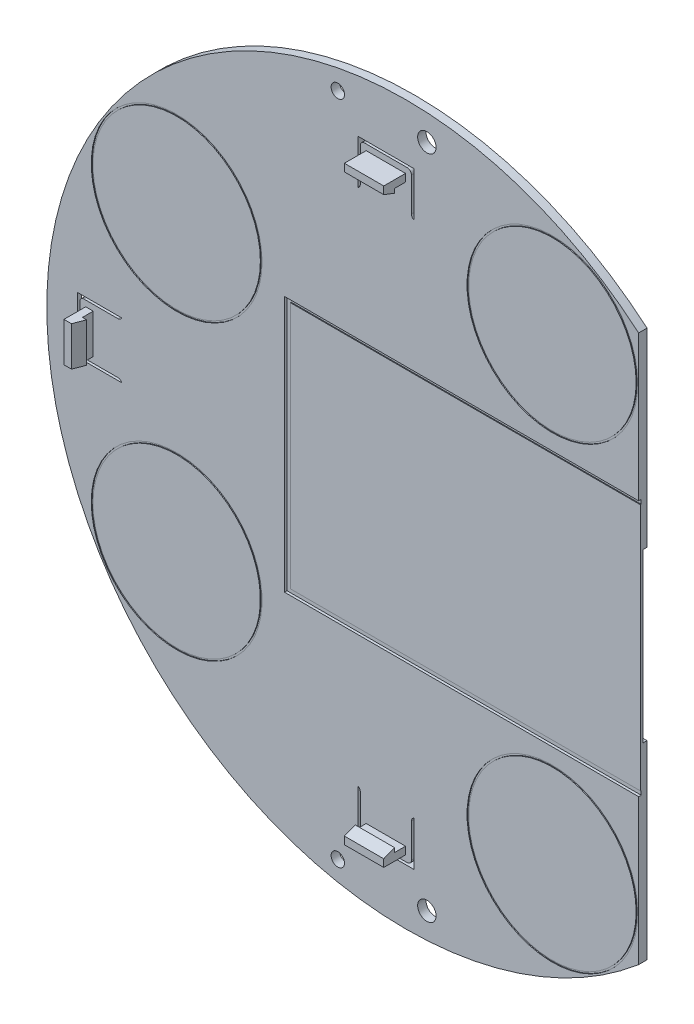
SolidWorks part; units mm, degrees
ref_plane "Front Plane" through (0, 0, 0) normal (1, 0, 0) x (0, 1, 0)
ref_plane "Top Plane" through (0, 0, 0) normal (0, 0, 1) x (0, 1, 0)
ref_plane "Right Plane" through (0, 0, 0) normal (0, 1, 0) x (-1, 0, 0)
sketch "Sketch1" plane through (0, 0, 0) normal (0, 0, 1) x (0, 1, 0)
  line L1 (0, 1.8938) -> (0, 57.7445) construction
  line L10 (65.3474, -55.6) -> (-65.3474, -55.6)
  circle A0 centre (-79.5, -5) radius 2.2
  arc A7 (65.3474, -55.6) -> (-65.3474, -55.6) centre (0, 0) ccw
  circle A9 centre (-79.5, 16.2726) radius 1.6
  circle A10 centre (79.5, 16.2726) radius 1.6
  circle A11 centre (79.5, -5) radius 2.2
  dimension "D1" = 85.8
  dimension "D2" = 55.6
  dimension "D3" = 5
  dimension "D4" = 79.5
  dimension "D5" = 16.2726
  dimension "D6" = 79.5
extrude "Boss-Extrude1" add sketch "Sketch1" along normal blind 2
sketch "Sketch3" plane through (0, 0, 2) normal (0, 0, 1) x (1, 0, 0)
  circle A0 centre (-54.772, 35.0004) radius 20
  circle A1 centre (-54.772, -35.0004) radius 20
  circle A2 centre (35, 54.7723) radius 20
  circle A3 centre (35, -54.7723) radius 20
  circle A5 centre (-54.772, 35.0004) radius 20.4
  circle A6 centre (-54.772, -35.0004) radius 20.4
  circle A7 centre (35, -54.7723) radius 20
  circle A9 centre (35, -54.7723) radius 20.4
  circle A10 centre (35, 54.7723) radius 20.4
extrude "Cut-Extrude9" cut sketch "Sketch3" against normal blind 0.2 contours A9 A3 | A10 A2 | A6 | A1 | A5 | A0 region at (14.6577, -54.7723, 2) region at (14.6577, 54.7723, 2)
sketch "Sketch6" plane through (0, 0, 2) normal (0, 0, 1) x (1, 0, 0)
  line L0 (-9.5, -70.5) -> (-9.5, -68.7)
  line L6 (-9.5, -70.5) -> (-0.1, -70.5)
  line L14 (-0.1, -70.5) -> (-0.1, -68.7)
  line L19 (-9.5, -68.7) -> (-0.1, -68.7)
  line L25 (0, 0) -> (-112.0525, 0) construction
  line L27 (-9.5, 68.7) -> (-0.1, 68.7)
  line L28 (-0.1, 70.5) -> (-0.1, 68.7)
  line L29 (-9.5, 70.5) -> (-0.1, 70.5)
  line L30 (-9.5, 70.5) -> (-9.5, 68.7)
  point P0 (-4.8, -69.9)
  point P11 (-4.8, 69.9)
extrude "Boss-Extrude2" add sketch "Sketch6" along normal blind 5.2
sketch "Sketch7" plane through (0, 0, 2) normal (0, 0, 1) x (1, 0, 0)
  line L0 (0, 0) -> (-76, 0) construction
  line L1 (-76.5, -4.7) -> (-76.5, 4.7)
  line L2 (-76.5, -4.7) -> (-74.7, -4.7)
  line L3 (-74.7, -4.7) -> (-74.7, 4.7)
  line L4 (-76.5, 4.7) -> (-74.7, 4.7)
extrude "Boss-Extrude3" add sketch "Sketch7" along normal blind 5.2
sketch "Sketch8" plane through (-0.1, 0, 0) normal (1, 0, 0) x (0, 1, 0)
  line L0 (-68.7, 7.2) -> (-68.7, 4.6)
  line L1 (-68.7, 7.2) -> (-68.7, 2) construction
  line L2 (-68.7, 4.6) -> (-67.7, 4.6)
  line L3 (-67.7, 4.6) -> (-68.7, 7.2)
  line L4 (0, 0) -> (0, 20.1599) construction
  line L5 (67.7, 4.6) -> (68.7, 7.2)
  line L6 (68.7, 4.6) -> (67.7, 4.6)
  line L7 (68.7, 7.2) -> (68.7, 4.6)
  line L8 (85.8, 2) -> (-85.8, 2) construction
  dimension "D1" = 1
  dimension "D2" = 2.6
extrude "Boss-Extrude4" add sketch "Sketch8" against normal blind 9.4
sketch "Sketch10" plane through (0, 0, 2) normal (0, 0, 1) x (1, 0, 0)
  line L0 (55.6, -29.6) -> (-28, -29.6)
  line L1 (55.6, -65.3474) -> (55.6, 65.3474) construction
  line L2 (55.6, 0) -> (-104.6824, 0) construction
  line L3 (-28, -29.6) -> (-28, 29.6)
  line L4 (55.6, -30.6) -> (-29, -30.6)
  line L5 (-29, -30.6) -> (-29, 30.6)
  line L6 (55.6, -30.6) -> (55.6, -29.6)
  line L7 (55.6, 30.6) -> (55.6, 29.6)
  line L8 (55.6, 30.6) -> (-29, 30.6)
  line L9 (55.6, 29.6) -> (-28, 29.6)
  point P14 (-29, 0)
  point P15 (-28, 0)
  dimension "D1" = 29.6
  dimension "D2" = 1
  dimension "D3" = 1
  dimension "D4" = 28
extrude "Cut-Extrude10" cut sketch "Sketch10" against normal blind 0.6
sketch "Sketch11" plane through (0, 0, 2) normal (0, 0, 1) x (1, 0, 0)
  line L1 (-28, 29.6) -> (55.6, 29.6)
  line L2 (-28, 29.6) -> (-28, -29.6)
  line L3 (-28, -29.6) -> (55.6, -29.6)
  line L4 (55.6, 29.6) -> (55.6, -29.6)
extrude "Cut-Extrude11" cut sketch "Sketch11" against normal blind 0.4
sketch "Sketch13" plane through (0, -4.7, 0) normal (0, -1, 0) x (1, 0, 0)
  line L0 (-74.7, 7.2) -> (-74.7, 4.6)
  line L1 (-74.7, 7.2) -> (-74.7, 2) construction
  line L2 (-74.7, 4.6) -> (-73.7, 4.6)
  line L3 (-73.7, 4.6) -> (-74.7, 7.2)
  line L4 (55.6, 2) -> (-85.8, 2) construction
  dimension "D1" = 1
  dimension "D2" = 2.6
extrude "Boss-Extrude5" add sketch "Sketch13" against normal blind 9.4
sketch "Sketch14" plane through (0, 0, 2) normal (0, 0, 1) x (1, 0, 0)
  line L0 (0.2, 71.5) -> (-9.8, 68.5) construction
  line L1 (-9.8, -71.5) -> (-9.8, -68.5)
  line L2 (-9.8, -71.5) -> (0.2, -71.5)
  line L3 (0.2, -71.5) -> (0.2, -68.5)
  line L4 (-9.8, -68.5) -> (0.2, -68.5)
  line L5 (-9.8, -71.5) -> (0.2, -68.5) construction
  line L6 (0.2, -71.5) -> (-9.8, -68.5) construction
  line L7 (-9.8, 71.5) -> (0.2, 68.5) construction
  line L8 (-9.8, 68.5) -> (0.2, 68.5)
  line L9 (0, 0) -> (-76, 0) construction
  line L10 (-77.5, -5) -> (-77.5, 5)
  line L11 (-77.5, -5) -> (-74.5, -5)
  line L12 (-74.5, -5) -> (-74.5, 5)
  line L13 (-77.5, 5) -> (-74.5, 5)
  line L14 (-77.5, -5) -> (-74.5, 5) construction
  line L15 (-74.5, -5) -> (-77.5, 5) construction
  line L16 (0.2, 71.5) -> (0.2, 68.5)
  line L17 (-9.8, 71.5) -> (0.2, 71.5)
  line L18 (-9.8, 71.5) -> (-9.8, 68.5)
  point P0 (-4.8, -70)
  point P10 (-4.8, 70)
sketch "Sketch15" plane through (0, 0, 0) normal (0, 0, -1) x (1, 0, 0)
  line L0 (-83.4364, 20) -> (55.6, 20)
  line L1 (55.6, 65.3474) -> (55.6, -65.3474) construction
  line L2 (0, 0) -> (-121.0707, 0) construction
  line L3 (-83.4364, -20) -> (55.6, -20)
  line L4 (55.6, 20) -> (55.6, -20)
  arc A1 (-83.4364, 20) -> (-83.4364, -20) centre (0, 0) ccw
  dimension "D1" = 20
extrude "Cut-Extrude12" cut sketch "Sketch15" against normal blind 1
sketch "Sketch16" plane through (0, 0, 2) normal (0, 0, 1) x (1, 0, 0)
sketch "Sketch17" plane through (0, 0, 2) normal (0, 0, 1) x (1, 0, 0)
  line L0 (-10.9, -71.9) -> (-10.9, -61.9)
  line L1 (-9.5, -70.5) -> (-0.1, -70.5) construction
  line L2 (-9.5, -68.7) -> (-9.5, -70.5) construction
  line L3 (-4.8, -70) -> (-4.8, -61.9) construction
  line L4 (-9.8, -71.5) -> (0.2, -68.5) construction
  line L5 (1.3, -71.9) -> (1.3, -61.9)
  line L6 (-10.9, -71.9) -> (1.3, -71.9)
  line L7 (-10.9, -61.9) -> (-11.5, -61.9)
  line L8 (-11.5, -61.9) -> (-11.5, -72.5)
  line L9 (1.3, -61.9) -> (1.9, -61.9)
  line L10 (1.9, -61.9) -> (1.9, -72.5)
  line L12 (0, 0) -> (-51.4634, 0) construction
  line L13 (0, 0) -> (-76, 0) construction
  line L15 (-11.5, -72.5) -> (1.9, -72.5)
  line L16 (1.9, 72.5) -> (-11.5, 72.5)
  line L17 (-78.5, 6.7) -> (-78.5, -6.7)
  line L35 (-4.8, 70) -> (-4.8, 61.9) construction
  line L36 (1.3, 71.9) -> (1.3, 61.9)
  line L37 (-10.9, 71.9) -> (-10.9, 61.9)
  line L38 (1.3, 61.9) -> (1.9, 61.9)
  line L39 (1.9, 61.9) -> (1.9, 72.5)
  line L40 (-10.9, 61.9) -> (-11.5, 61.9)
  line L41 (-11.5, 61.9) -> (-11.5, 72.5)
  line L62 (-10.9, 71.9) -> (1.3, 71.9)
  line L65 (-77.9, 6.1) -> (-67.9, 6.1)
  line L66 (-76, 0) -> (-67.9, 0) construction
  line L67 (-77.9, -6.1) -> (-67.9, -6.1)
  line L68 (-77.9, 6.1) -> (-77.9, -6.1)
  line L69 (-67.9, 6.1) -> (-67.9, 6.7)
  line L70 (-67.9, 6.7) -> (-78.5, 6.7)
  line L71 (-67.9, -6.1) -> (-67.9, -6.7)
  line L72 (-67.9, -6.7) -> (-78.5, -6.7)
  dimension "D1" = 1.4
  dimension "D2" = 1.4
  dimension "D3" = 10
  dimension "D4" = 0.6
  dimension "D5" = 0.6
  dimension "D6" = 0.6
extrude "Cut-Extrude13" cut sketch "Sketch17" against normal blind 10
fillet "Fillet1" radius 1 1 edges at (-10.9, -71.9, 1)
fillet "Fillet4" radius 1 2 edges at (1.3, -61.9, 1) (1.3, -71.9, 1)
fillet "Fillet8" radius 1 1 edges at (-10.9, -61.9, 1)
fillet "Fillet9" radius 1 4 edges at (-10.9, 61.9, 1) (1.3, 61.9, 1) (1.3, 71.9, 1) (-10.9, 71.9, 1)
fillet "Fillet10" radius 1 4 edges at (-77.9, -6.1, 1.5) (-67.9, -6.1, 1.5) (-67.9, 6.1, 1.5) (-77.9, 6.1, 1.5)
